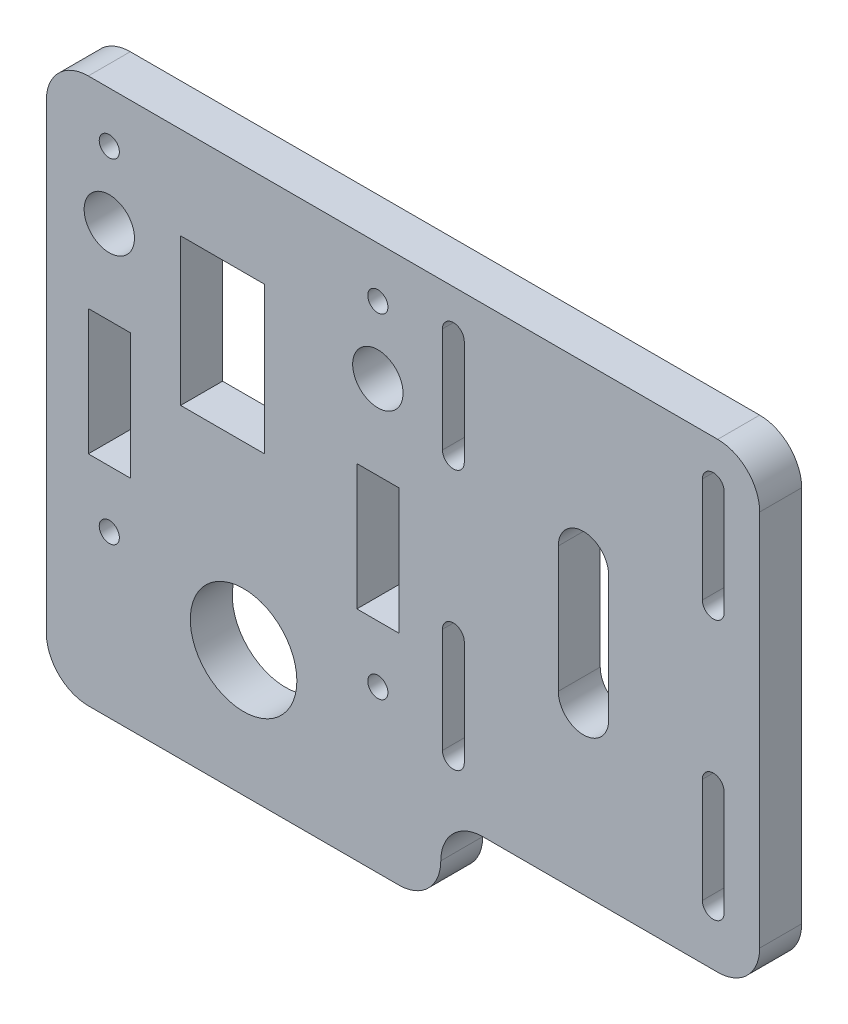
SolidWorks part; units mm, degrees
material "Acrylic (Medium-high impact)"
ref_plane "Front Plane" through (0, 0, 0) normal (0, 0, 1) x (1, 0, 0)
ref_plane "Top Plane" through (0, 0, 0) normal (0, 1, 0) x (1, 0, 0)
ref_plane "Right Plane" through (0, 0, 0) normal (1, 0, 0) x (0, 0, -1)
sketch "Sketch1" plane through (0, 0, 0) normal (0, 0, 1) x (1, 0, 0)
  line L0 (0, 65) -> (0, 0) construction
  line L1 (-23.5, 65) -> (23.5, 65)
  line L2 (13.5, 41) -> (18.5, 41)
  line L3 (-23.5, 0) -> (0, 0)
  line L4 (13.5, 41) -> (13.5, 26)
  line L5 (13.5, 26) -> (18.5, 26)
  line L6 (18.5, 41) -> (18.5, 26)
  line L9 (-7.5, 54) -> (2.5, 54)
  line L10 (-7.5, 54) -> (-7.5, 36.5)
  line L11 (-7.5, 36.5) -> (2.5, 36.5)
  line L12 (-18.5, 41) -> (-18.5, 26)
  line L13 (-13.5, 26) -> (-18.5, 26)
  line L14 (-13.5, 41) -> (-13.5, 26)
  line L15 (-13.5, 41) -> (-18.5, 41)
  line L16 (-23.5, 65) -> (-23.5, 0)
  line L20 (0, 0) -> (23.5, 0)
  line L21 (23.5, 65) -> (23.5, 0)
  line L35 (2.5, 54) -> (2.5, 36.5)
  circle A0 centre (16, 51) radius 3
  circle A1 centre (16, 19.2) radius 1.2
  circle A2 centre (16, 59) radius 1.2
  circle A3 centre (-16, 59) radius 1.2
  circle A4 centre (-16, 19.2) radius 1.2
  circle A5 centre (-16, 51) radius 3
  circle A6 centre (0, 15) radius 6.35
  point P34 (-16, 106)
  dimension "D3" = 65
  dimension "D4" = 2.4
  dimension "D16" = 12.7
  dimension "D18" = 6.8
  dimension "D6" = 5
  dimension "D8" = 50
  dimension "D9" = 15
  dimension "D10" = 6
  dimension "D11" = 8
  dimension "D12" = 17.5
  dimension "D13" = 10
  dimension "D14" = 6
  dimension "D17" = 10
  dimension "D24" = 2
  dimension "D27" = 3
extrude "Boss-Extrude1" add sketch "Sketch1" along normal blind 5
sketch "Sketch2" plane through (0, 0, 0) normal (0, 0, -1) x (-1, 0, 0)
  line L0 (-40.5, 44.5) -> (-40.5, 29.5) construction
  line L1 (-23.5, 65) -> (-61.5, 65)
  line L2 (-23.5, 65) -> (-23.5, 10)
  line L3 (-23.5, 10) -> (-61.5, 10)
  line L4 (-61.5, 65) -> (-61.5, 10)
  line L5 (-37.5, 44.5) -> (-37.5, 29.5)
  line L6 (-43.5, 44.5) -> (-43.5, 29.5)
  line L7 (-25, 60) -> (-25, 47.5) construction
  line L8 (-23.7, 60) -> (-23.7, 47.5)
  line L9 (-26.3, 60) -> (-26.3, 47.5)
  line L10 (-55.9683, 60) -> (-55.9683, 47.5) construction
  line L11 (-54.6683, 60) -> (-54.6683, 47.5)
  line L12 (-57.2683, 60) -> (-57.2683, 47.5)
  line L13 (-25, 29) -> (-25, 16.5) construction
  line L14 (-23.7, 29) -> (-23.7, 16.5)
  line L15 (-26.3, 29) -> (-26.3, 16.5)
  line L16 (-55.9683, 29) -> (-55.9683, 16.5) construction
  line L17 (-54.6683, 29) -> (-54.6683, 16.5)
  line L18 (-57.2683, 29) -> (-57.2683, 16.5)
  arc A0 (-37.5, 44.5) -> (-43.5, 44.5) centre (-40.5, 44.5) ccw
  arc A1 (-43.5, 29.5) -> (-37.5, 29.5) centre (-40.5, 29.5) ccw
  arc A2 (-23.7, 60) -> (-26.3, 60) centre (-25, 60) ccw
  arc A3 (-26.3, 47.5) -> (-23.7, 47.5) centre (-25, 47.5) ccw
  arc A4 (-54.6683, 60) -> (-57.2683, 60) centre (-55.9683, 60) ccw
  arc A5 (-57.2683, 47.5) -> (-54.6683, 47.5) centre (-55.9683, 47.5) ccw
  arc A6 (-23.7, 29) -> (-26.3, 29) centre (-25, 29) ccw
  arc A7 (-26.3, 16.5) -> (-23.7, 16.5) centre (-25, 16.5) ccw
  arc A8 (-54.6683, 29) -> (-57.2683, 29) centre (-55.9683, 29) ccw
  arc A9 (-57.2683, 16.5) -> (-54.6683, 16.5) centre (-55.9683, 16.5) ccw
  point P7 (-40.5, 37)
  point P14 (-25, 53.75)
  point P23 (-55.9683, 53.75)
  point P30 (-25, 22.75)
  point P37 (-55.9683, 22.75)
  dimension "D2" = 3
  dimension "D7" = 1.3
  dimension "D1" = 38
  dimension "D3" = 15
  dimension "D4" = 12.5
  dimension "D5" = 15.5
  dimension "D6" = 15.5
  dimension "D8" = 2
  dimension "D10" = 55
  dimension "D11" = 5
  dimension "D12" = 17
  dimension "D9" = 2
extrude "Boss-Extrude2" add sketch "Sketch2" against normal blind 5
fillet "Fillet1" radius 5 6 edges at (23.5, 0, 2.5) (-23.5, 0, 2.5) (-23.5, 65, 2.5) (61.5, 10, 2.5) (61.5, 65, 2.5)
